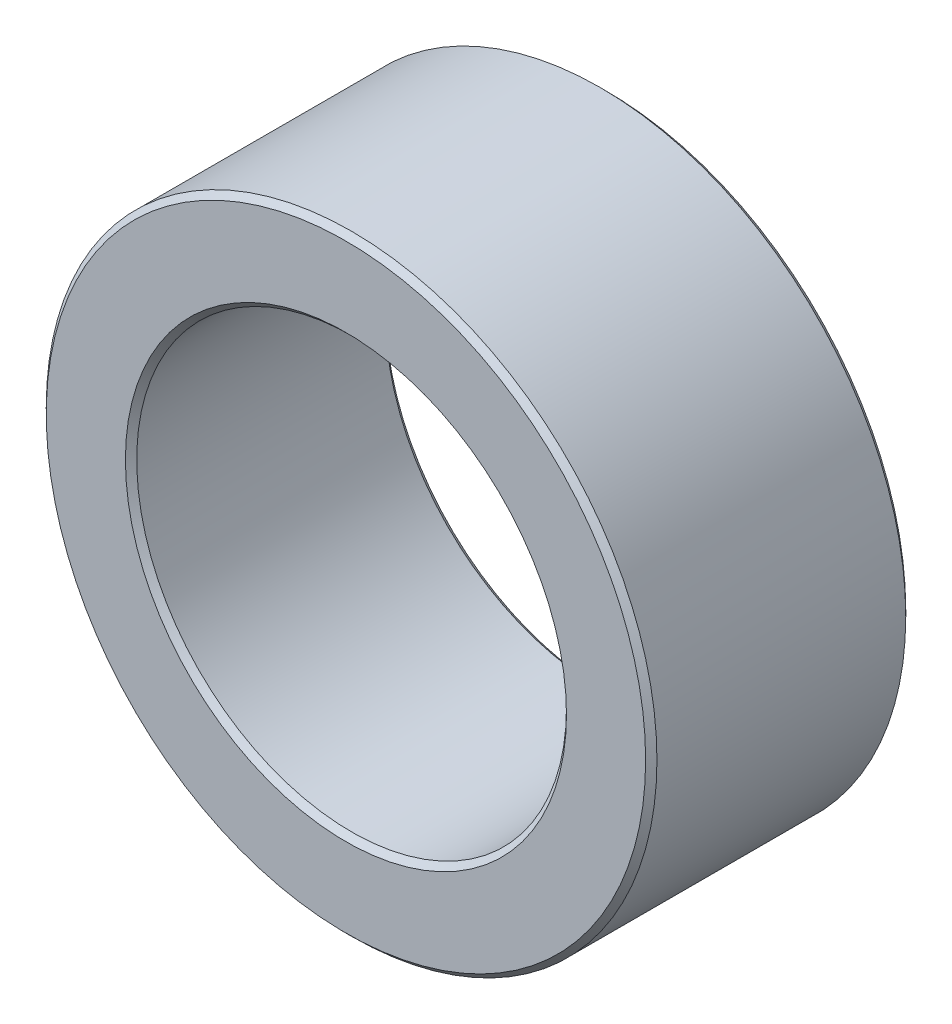
SolidWorks part; units mm, degrees
material "1.0037 (S235JR)"
ref_plane "E_Rechts" through (0, 0, 0) normal (0, 0, 1) x (1, 0, 0)
ref_plane "E_Oben" through (0, 0, 0) normal (0, 1, 0) x (1, 0, 0)
ref_plane "E_Vorne" through (0, 0, 0) normal (1, 0, 0) x (0, 0, -1)
ref_axis "A_Drehachse" through (0, 0, -88.99) along (0, 0, 1)
sketch "Skizze1" plane through (0, 0, 0) normal (0, 0, 1) x (1, 0, 0)
  circle A0 centre (0, 0) radius 19
  circle A1 centre (0, 0) radius 27
  dimension "D1" = 54
  dimension "D2" = 38
extrude "Aufsatz-Linear austragen1" add sketch "Skizze1" along normal mid plane 23
chamfer "Fase1" distance 0.5 angle 45 4 edges at (19, 0, -11.5) (27, 0, -11.5) (27, 0, 11.5) (19, 0, 11.5)
